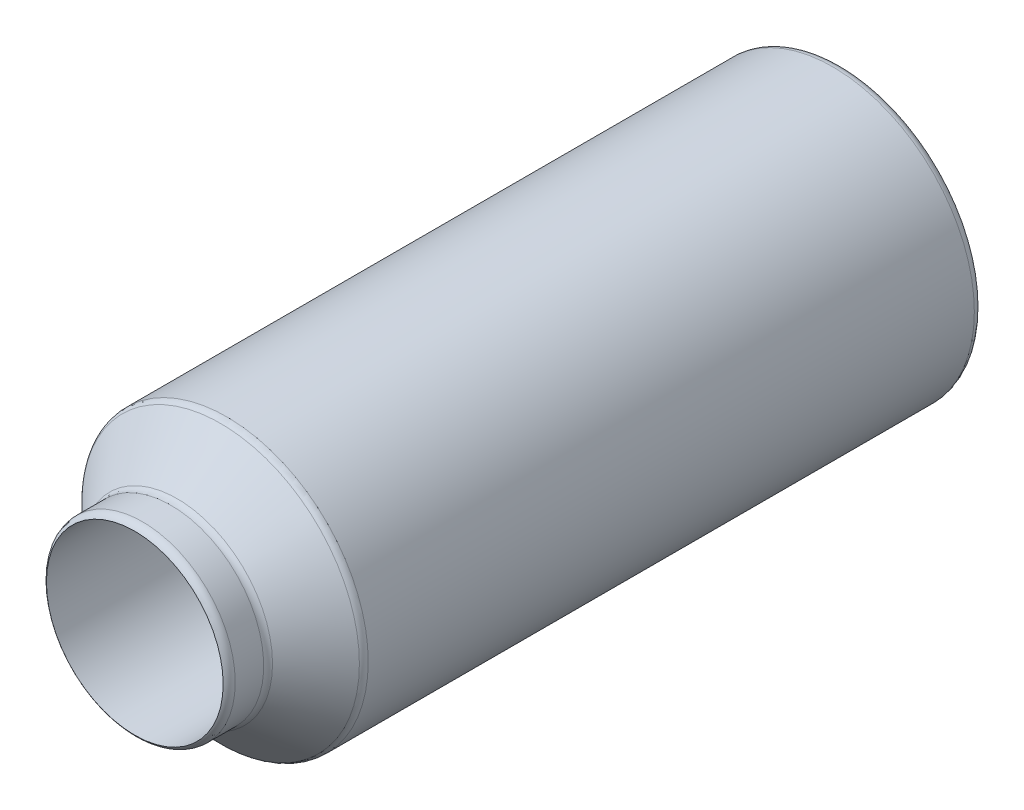
SolidWorks part; units mm, degrees
ref_plane "Front Plane" through (0, 0, 0) normal (0, 0, 1) x (1, 0, 0)
ref_plane "Top Plane" through (0, 0, 0) normal (0, 1, 0) x (1, 0, 0)
ref_plane "Right Plane" through (0, 0, 0) normal (1, 0, 0) x (0, 0, -1)
sketch "Sketch3" plane through (0, 0, 0) normal (0, 1, 0) x (1, 0, 0)
  line L0 (8, 0) -> (8, -35)
  line L4 (8, 0) -> (5, 0)
  line L5 (5, 0) -> (5, -40)
  line L6 (8, -35) -> (5.25, -37.75)
  line L7 (5.25, -37.75) -> (5.25, -40)
  line L8 (5.25, -40) -> (5, -40)
  line L9 (0, 0) -> (0, -16.8345) construction
  dimension "D1" = 40
  dimension "D2" = 0.25
  dimension "D3" = 5
  dimension "D4" = 3
  dimension "D5" = 5
  dimension "D6" = 135
revolve "Revolve2" add sketch "Sketch3" angle 360 about L9
fillet "Fillet1" radius 0.5 5 edges at (-5.25, 0, 40) (-5.25, 0, 37.75) (-8, 0, 35) (-5, 0, 0) (-8, 0, 0)
